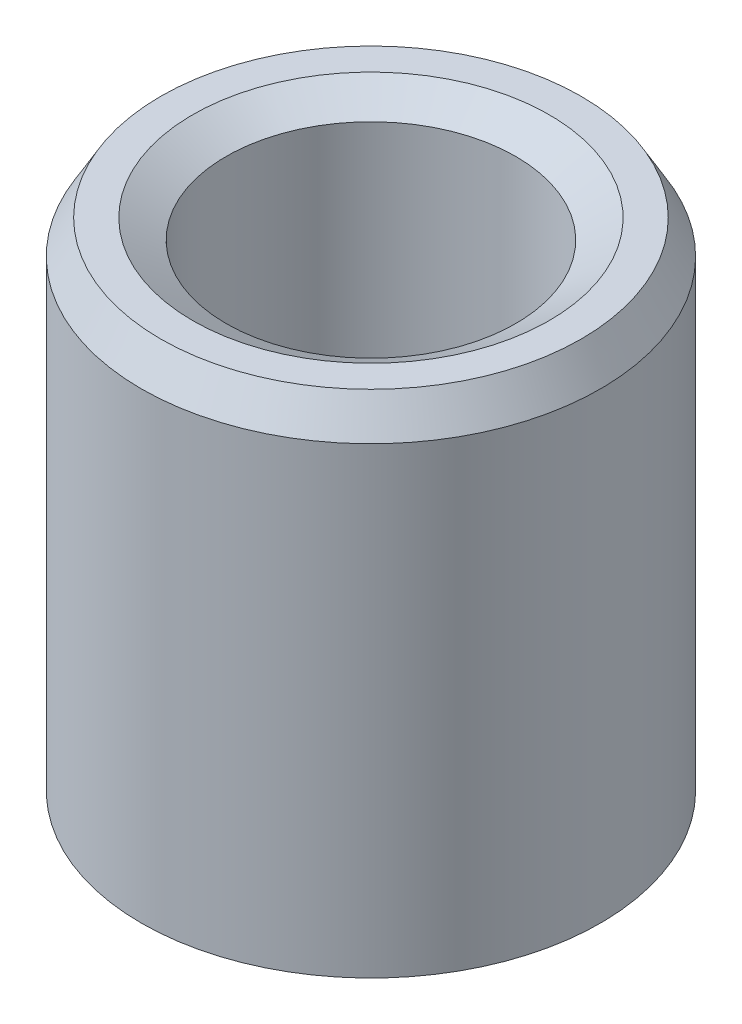
SolidWorks part; units mm, degrees
ref_plane "Front Plane" through (0, 0, 0) normal (0, 0, 1) x (1, 0, 0)
ref_plane "Top Plane" through (0, 0, 0) normal (0, 1, 0) x (1, 0, 0)
ref_plane "Right Plane" through (0, 0, 0) normal (1, 0, 0) x (0, 0, -1)
sketch "Sketch1" plane through (0, 0, 0) normal (0, 1, 0) x (1, 0, 0)
  circle A0 centre (0, 0) radius 17.5
  dimension "SLEEVE_OD" = 35
extrude "Boss-Extrude1" add sketch "Sketch1" along normal blind 39.2981
sketch "Sketch2" plane through (0, 0, 0) normal (0, 1, 0) x (1, 0, 0)
  circle A0 centre (0, 0) radius 11.0391
  dimension "BORE_D" = 22.0783
extrude "Cut-Extrude1" cut sketch "Sketch2" along normal through all
chamfer "Chamfer1" distance 2.5532 angle 30 4 edges at (0, 39.2981, 11.0391) (0, 0, 11.0391) (0, 0, 17.5) (0, 39.2981, 17.5) first distance on face at (0, 39.2981, 11.0391) first distance on face at (0, 0, 11.0391) first distance on face at (0, 39.2981, 17.5)
